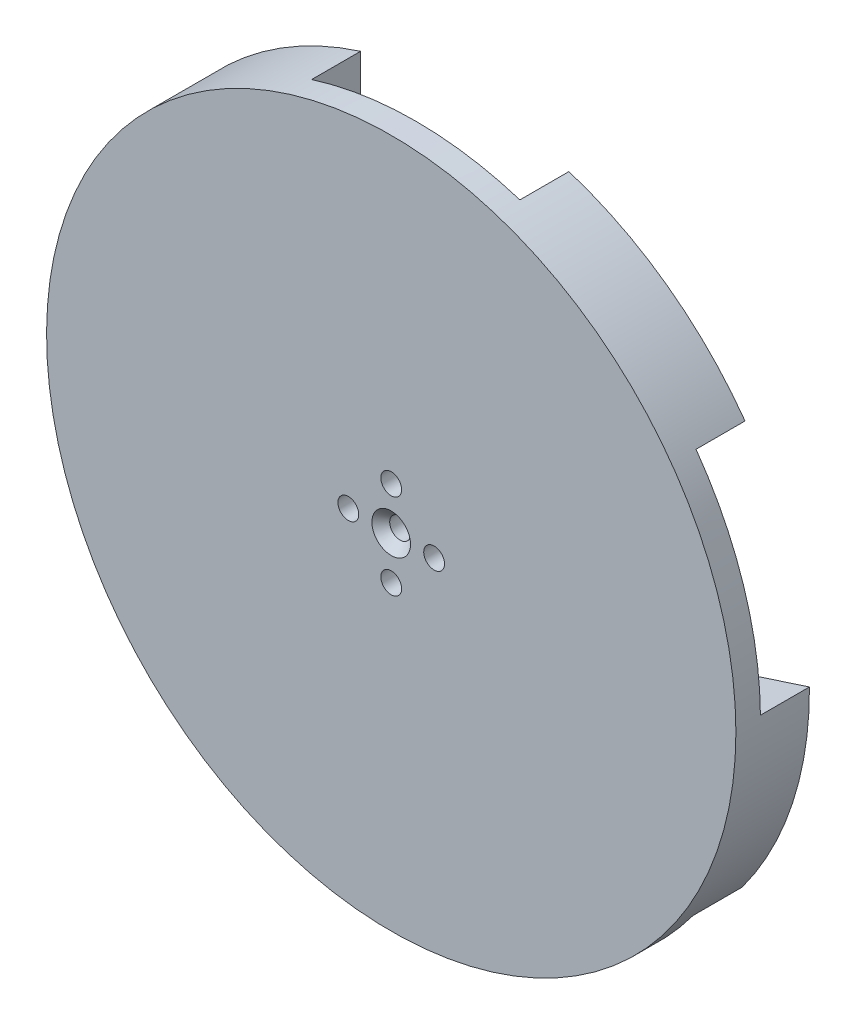
SolidWorks part; units mm, degrees
ref_plane "Front Plane" through (0, 0, 0) normal (0, 0, 1) x (1, 0, 0)
ref_plane "Top Plane" through (0, 0, 0) normal (0, 1, 0) x (1, 0, 0)
ref_plane "Right Plane" through (0, 0, 0) normal (1, 0, 0) x (0, 0, -1)
sketch "Sketch2" plane through (0, 0, 0) normal (0, 0, 1) x (1, 0, 0)
  line L0 (0, 10) -> (0, 0) construction
  line L1 (0, 0) -> (0, -10) construction
  line L3 (0, -10) -> (0, -56.25) construction
  line L4 (-56.25, 0) -> (-10, 0) construction
  line L5 (-10, 0) -> (0, 0) construction
  line L6 (0, 0) -> (10, 0) construction
  line L7 (10, 0) -> (56.25, 0) construction
  line L8 (0, 56.25) -> (0, 34.65) construction
  line L9 (0, 34.65) -> (0, 10) construction
  circle A0 centre (0, 0) radius 56.25
  point P6 (0, -33.125)
  point P8 (0, 34.65)
  point P13 (-33.125, 0)
  point P14 (33.125, 0)
  dimension "D1" = 112.5
  dimension "D2" = 20
  dimension "D3" = 21.6
extrude "Boss-Extrude1" add sketch "Sketch2" along normal blind 12
sketch "Sketch3" plane through (0, 0, 0) normal (0, 0, -1) x (-1, 0, 0)
  line L1 (-17, 34.65) -> (-17, 53.6196)
  line L2 (17, 34.65) -> (17, 53.6196)
  arc A0 (-17, 34.65) -> (17, 34.65) centre (0, 34.65) ccw
  circle A2 centre (0, 0) radius 56.25 construction
  arc A10 (17, 53.6196) -> (-17, 53.6196) centre (0, 0) ccw
  dimension "D1" = 34
sketch "Sketch4" plane through (0, 0, 0) normal (0, 0, -1) x (-1, 0, 0)
  line L0 (-10, 0) -> (-7, 0) construction
  line L1 (-7, 0) -> (0, 0) construction
  line L2 (0, 0) -> (7, 0) construction
  line L3 (7, 0) -> (10, 0) construction
  line L4 (0, -10) -> (0, -7) construction
  line L5 (0, -7) -> (0, 0) construction
  line L6 (0, 0) -> (0, 7) construction
  line L7 (0, 7) -> (0, 10) construction
  circle A0 centre (0, 0) radius 10
  dimension "D1" = 20
  dimension "D2" = 14
extrude "Cut-Extrude2" cut sketch "Sketch4" against normal blind 2
hole_wizard "M3 Clearance Hole1" positions "Sketch5" profile "Sketch6" hole size "M3" standard "ANSI Metric"
sketch "Sketch5" plane through (0, 0, 2) normal (0, 0, -1) x (-1, 0, 0)
  point P0 (7, 0)
  point P3 (0, 7)
  point P6 (-7, 0)
  point P9 (0, -7)
sketch "Sketch6" plane through (-7, 0, 2) normal (1, 0, 0) x (0, 1, 0)
  line L0 (0, 0) -> (0, 11.0215)
  line L1 (0, 11.0215) -> (1.7, 10)
  line L2 (1.7, 10) -> (1.7, 0)
  line L5 (1.7, 0) -> (0, 0)
  line L10 (0, 11.0215) -> (-1.7, 10) construction
  line L11 (0, -6.35) -> (0, 107.95) construction
  dimension "Hole Dia." = 3.4
  dimension "Hole Depth" = 10
  dimension "Drill Angle" = 118
hole_wizard "CSK for M3 Flat Head Machine Screw2" positions "Sketch9" profile "Sketch10" countersink size "M3" standard "ANSI Metric"
sketch "Sketch9" plane through (0, 0, 12) normal (0, 0, 1) x (1, 0, 0)
  point P0 (0, 0)
sketch "Sketch10" plane through (0, 0, 12) normal (1, 0, 0) x (0, -1, 0)
  line L0 (0, 0) -> (0, 11.0215)
  line L1 (0, 11.0215) -> (1.7, 10)
  line L2 (1.7, 10) -> (1.7, 1.45)
  line L3 (1.7, 1.45) -> (3.15, 0)
  line L5 (3.15, 0) -> (0, 0)
  line L6 (-1.7, 1.45) -> (-3.15, 0) construction
  line L10 (0, 11.0215) -> (-1.7, 10) construction
  line L11 (0, -6.35) -> (0, 107.95) construction
  dimension "Hole Dia." = 3.4
  dimension "Hole Depth" = 10
  dimension "Near C'Sink Dia." = 6.3
  dimension "Near C'Sink Angle" = 90
  dimension "Drill Angle" = 118
extrude "Cut-Extrude3" cut sketch "Sketch3" against normal blind 8
pattern_circular "CirPattern1" count 5 over 360 about axis through (0, 0, 12) along (0, 0, -1) of "Cut-Extrude3"
sketch "Sketch11" plane through (0, 0, 8) normal (0, 0, -1) x (-1, 0, 0)
  circle A0 centre (0, 34.65) radius 5.25
  dimension "D1" = 10.5
extrude "Cut-Extrude4" cut sketch "Sketch11" against normal blind 2.5
equation "\"board_length\"= 260mm"
equation "\"board_height\"= 200mm"
equation "\"board_width\"= 16.5mm"
equation "\"token_thickness\"= 7mm"
equation "\"token_diameter\"= 32mm"
equation "\"board_side_lower_height\"= 55mm"
equation "\"board_side_height\"= 156.5mm"
equation "\"board_side_length\"= 100mm"
equation "\"board_slot_width\"= \"board_length\" / 7"
equation "\"token_ridge\"= ( \"token_thickness\" - 4mm ) / 2"
equation "\"token_ridge_width\"= 1.5mm"
equation "\"25T_outer_diameter\"= 20mm"
equation "\"25T_inner_diameter\"= 9mm"
equation "\"2T_screw_distance\" = 14mm"
equation "\"2T_outer_thickness\"= 2mm"
equation "\"2T_inner_thickness\"= 4.5mm"
equation "\"D1@Sketch2\"=\"MG996R_outer_length\"*2+4.5mm"
equation "\"D2@Sketch2\"=\"25T_outer_diameter\""
equation "\"D1@Boss-Extrude1\"=\"dispenser_wheel_width\""
equation "\"D1@Sketch3\"=\"token_diameter\"+2.0mm"
equation "\"D1@Sketch4\"=\"25T_outer_diameter\""
equation "\"D1@Cut-Extrude2\"=\"2T_outer_thickness\""
equation "\"D2@Sketch4\"=\"2T_screw_distance\""
equation "\"MG996R_outer_length\"= 54mm"
equation "\"MG996R_inner_length\"= 40mm"
equation "\"MG996R_width\"= 20mm"
equation "\"MG996R_height\" = 26.6mm"
equation "\"MG996R_full_height\"= 45.7mm"
equation "\"MG996R_full_width\"= 55.5mm"
equation "\"MG996R_screw_distance\"= 10mm"
equation "\"D1@Cut-Extrude3\"=\"token_thickness\"+1mm"
equation "\"magnet_diameter\" = 10mm"
equation "\"D1@Sketch11\"=\"magnet_diameter\"+0.5mm"
equation "\"magnet_thickness\"= 2mm"
equation "\"D1@Cut-Extrude4\"=\"magnet_thickness\"+0.5mm"
equation "\"dispenser_barrel_margin\"= 2.5mm"
equation "\"dispenser_wheel_width\"= \"token_thickness\" + 5mm"
equation "\"D3@Sketch2\"=\"token_diameter\"/2*1.35"
